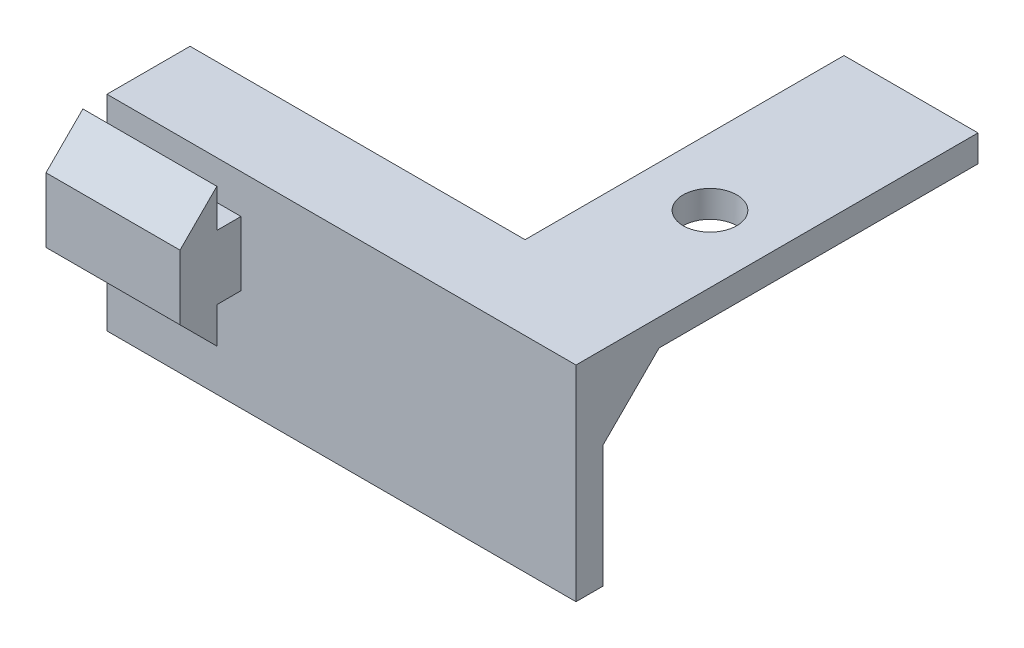
SolidWorks part; units mm, degrees
note: The reader was unsure of these and kept them because the rebuilt part matched: shared geometry of "Sketch1<14>", "Sketch1<18>".
ref_plane "Front Plane" through (0, 0, 0) normal (0, 0, 1) x (1, 0, 0)
ref_plane "Top Plane" through (0, 0, 0) normal (0, 1, 0) x (1, 0, 0)
ref_plane "Right Plane" through (0, 0, 0) normal (1, 0, 0) x (0, 0, -1)
sketch "Sketch1" plane through (0, 0, 0) normal (1, 0, 0) x (0, 0, -1)
  line L0 (0, 0) -> (0, 20)
  line L1 (0, 20) -> (30, 20)
  line L2 (30, 20) -> (30, 19)
  line L3 (2, 0) -> (2, 13.3)
  line L4 (2, 15.3) -> (0, 15.3)
  line L5 (2, 0) -> (0, 0)
  line L6 (0, 9.1) -> (2, 9.1) construction
  line L7 (0, 9.1) -> (-1.8, 9.1) construction
  line L8 (30, 19) -> (2, 19)
  line L9 (2, 19) -> (2, 15.3)
  line L10 (2, 15.3) -> (30, 15.3)
  line L11 (30, 15.3) -> (30, 13.3)
  line L12 (30, 13.3) -> (2, 13.3)
  line L13 (-1.8, 9.1) -> (-1.8, 12.4) construction
  line L14 (-1.8, 12.4) -> (-1.8, 15.25)
  line L15 (-1.8, 15.25) -> (-4.55, 12.5)
  line L16 (-1.8, 9.1) -> (-1.8, 7.6) construction
  line L17 (-1.8, 7.6) -> (-1.8, 4.9217)
  line L18 (-1.8, 4.9217) -> (-4.55, 7.6717)
  line L19 (-4.55, 12.5) -> (-4.55, 7.6717)
  line L20 (-1.8, 12.4) -> (0, 12.4)
  line L21 (-1.8, 7.6) -> (0, 7.6)
  line L22 (2, 9.1) -> (6.2, 13.3)
  line L23 (6.2, 13.3) -> (6.2, 15.3)
  dimension "D1" = 20
  dimension "D2" = 13.3
  dimension "D3" = 2
  dimension "D4" = 2
  dimension "D5" = 30
extrude "Boss-Extrude2" add sketch "Sketch1" along normal blind 10
sketch "Sketch2" plane through (0, 15.3, 0) normal (0, 1, 0) x (1, 0, 0)
  line L0 (0, 15) -> (10, 15)
  line L1 (0, 0) -> (0, 30) construction
  line L2 (10, 0) -> (10, 30) construction
  circle A0 centre (5, 15) radius 2
extrude "Cut-Extrude9" cut sketch "Sketch2" against normal blind 3 contours L0 A0 | L0 A0
extrude "Boss-Extrude3" add sketch "Sketch1<14>" against normal blind 25 contours L12 L11 L10 L4 L0 L5 L3 | L3 L22 L12 | L17 L21 L0 L20 L14 L15 L19 L18
sketch "Sketch1<14>" plane through (0, 0, 0) normal (1, 0, 0) x (0, 0, -1) same geometry as "Sketch1"
extrude "Cut-Extrude11" cut sketch "Sketch1<18>" against normal blind 15 contours L17 L21 L0 L20 L14 L15 L19 L18
sketch "Sketch1<18>" plane through (0, 0, 0) normal (1, 0, 0) x (0, 0, -1) same geometry as "Sketch1"
